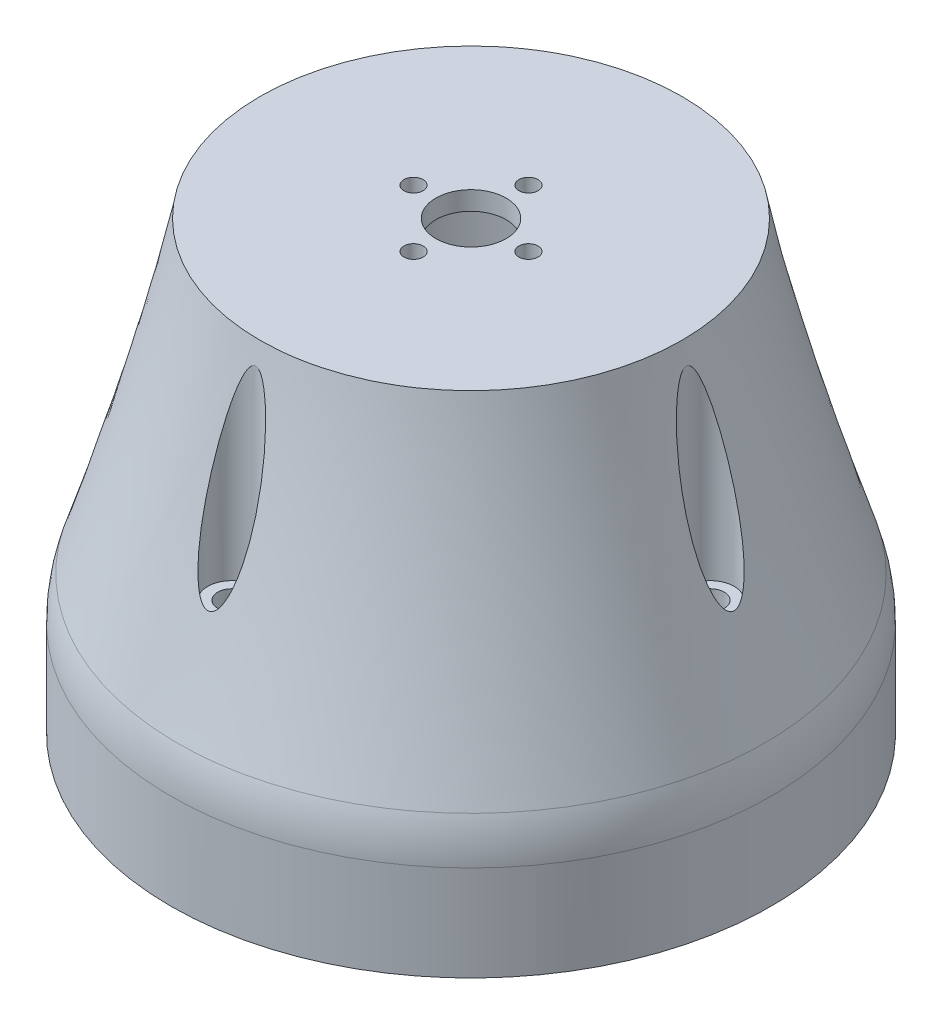
SolidWorks part; units mm, degrees
ref_plane "Front Plane" through (0, 0, 0) normal (0, 0, 1) x (1, 0, 0)
ref_plane "Top Plane" through (0, 0, 0) normal (0, 1, 0) x (1, 0, 0)
ref_plane "Right Plane" through (0, 0, 0) normal (1, 0, 0) x (0, 0, -1)
sketch "Sketch3" plane through (0, 0, 0) normal (0, 1, 0) x (1, 0, 0)
  circle A0 centre (0, 0) radius 64
  dimension "D1" = 128
extrude "Boss-Extrude1" add sketch "Sketch3" along normal blind 15
ref_plane "Plane1" through (0, 85, 0) normal (0, 1, 0) x (1, 0, 0)
sketch "Sketch4" plane through (0, 85, 0) normal (0, 1, 0) x (1, 0, 0)
  circle A0 centre (0, 0) radius 45
  dimension "D1" = 90
sketch "Sketch5" plane through (0, 15, 0) normal (0, 1, 0) x (1, 0, 0)
  circle A1 centre (0, 0) radius 64
  circle A2 centre (0, 0) radius 64
  dimension "D1" = 0
loft "Loft1" add profiles "Sketch5", "Sketch4" connector at (-2.5729, 15, 63.9483) connector at (15.8799, 85, 42.105)
fillet "Fillet1" radius 30 1 edges at (0, 15, 64) type face fillet first side face at (0, 15, 64) second side face at (0, 15, 64)
sketch "Sketch6" plane through (0, 85, 0) normal (0, 1, 0) x (1, 0, 0)
  circle A0 centre (0, 0) radius 51 construction
  circle A1 centre (0, 51) radius 3
  circle A2 centre (51, 0) radius 3
  circle A3 centre (0, -51) radius 3
  circle A4 centre (-51, 0) radius 3
  point P14 (0, 0)
  dimension "D1" = 102
  dimension "D2" = 6
  dimension "D3" = 4
extrude "Cut-Extrude1" cut sketch "Sketch6" against normal blind 85
sketch "Sketch8" plane through (0, 85, 0) normal (0, 1, 0) x (1, 0, 0)
  circle A0 centre (-51, 0) radius 5.11
  circle A1 centre (0, 51) radius 5.11
  circle A2 centre (51, 0) radius 5.11
  circle A3 centre (0, -51) radius 5.11
  point P12 (0, 0)
  dimension "D1" = 10.22
  dimension "D2" = 4
extrude "Cut-Extrude3" cut sketch "Sketch8" against normal blind 45
sketch "Sketch9" plane through (0, 0, 0) normal (0, -1, 0) x (1, 0, 0)
  arc A0 (-16.4684, 53.5238) -> (-53.5238, 16.4684) centre (0, 0) ccw
  arc A1 (-7.1314, 48.6777) -> (7.1314, 48.6777) centre (0, 51) ccw
  arc A5 (-7.1314, 48.6777) -> (-16.4684, 53.5238) centre (-14.2628, 46.3554) ccw
  arc A6 (16.4684, 53.5238) -> (7.1314, 48.6777) centre (14.2628, 46.3554) ccw
  arc A7 (48.6777, 7.1314) -> (53.5238, 16.4684) centre (46.3554, 14.2628) ccw
  arc A8 (48.6777, 7.1314) -> (48.6777, -7.1314) centre (51, 0) ccw
  arc A9 (53.5238, -16.4684) -> (48.6777, -7.1314) centre (46.3554, -14.2628) ccw
  arc A10 (7.1314, -48.6777) -> (16.4684, -53.5238) centre (14.2628, -46.3554) ccw
  arc A11 (7.1314, -48.6777) -> (-7.1314, -48.6777) centre (0, -51) ccw
  arc A12 (-16.4684, -53.5238) -> (-7.1314, -48.6777) centre (-14.2628, -46.3554) ccw
  arc A13 (-48.6777, -7.1314) -> (-53.5238, -16.4684) centre (-46.3554, -14.2628) ccw
  arc A14 (-48.6777, -7.1314) -> (-48.6777, 7.1314) centre (-51, 0) ccw
  arc A15 (-53.5238, 16.4684) -> (-48.6777, 7.1314) centre (-46.3554, 14.2628) ccw
  arc A16 (53.5238, 16.4684) -> (16.4684, 53.5238) centre (0, 0) ccw
  arc A17 (16.4684, -53.5238) -> (53.5238, -16.4684) centre (0, 0) ccw
  arc A18 (-53.5238, -16.4684) -> (-16.4684, -53.5238) centre (0, 0) ccw
  point P15 (0, 0)
  point P35 (0, 0)
  dimension "D1" = 112
  dimension "D2" = 15
  dimension "D3" = 4
  dimension "D4" = 15
  dimension "D5" = 15
extrude "Cut-Extrude4" cut sketch "Sketch9" against normal blind 12
sketch "Sketch17" plane through (0, 12, 0) normal (0, -1, 0) x (1, 0, 0)
  circle A0 centre (0, 0) radius 29
  dimension "D1" = 58
extrude "Cut-Extrude10" cut sketch "Sketch17" against normal blind 69
sketch "Sketch19" plane through (0, 0, 0) normal (0, -1, 0) x (1, 0, 0)
  arc A0 (16.4684, -53.5238) -> (53.5238, -16.4684) centre (0, 0) ccw construction
  circle A1 centre (0, 0) radius 64
  circle A2 centre (0, 0) radius 64
  arc A3 (53.5238, -16.4684) -> (48.6777, -7.1314) centre (46.3554, -14.2628) ccw construction
  arc A4 (48.6777, 7.1314) -> (48.6777, -7.1314) centre (51, 0) ccw construction
  arc A5 (48.6777, 7.1314) -> (53.5238, 16.4684) centre (46.3554, 14.2628) ccw construction
  arc A6 (53.5238, 16.4684) -> (16.4684, 53.5238) centre (0, 0) ccw construction
  arc A7 (-7.1314, 48.6777) -> (7.1314, 48.6777) centre (0, 51) ccw construction
  arc A8 (-7.1314, 48.6777) -> (-16.4684, 53.5238) centre (-14.2628, 46.3554) ccw construction
  arc A9 (16.4684, -53.5238) -> (53.5238, -16.4684) centre (0, 0) ccw
  arc A10 (53.5238, -16.4684) -> (48.6777, -7.1314) centre (46.3554, -14.2628) ccw
  arc A11 (48.6777, 7.1314) -> (48.6777, -7.1314) centre (51, 0) ccw
  arc A12 (48.6777, 7.1314) -> (53.5238, 16.4684) centre (46.3554, 14.2628) ccw
  arc A13 (53.5238, 16.4684) -> (16.4684, 53.5238) centre (0, 0) ccw
  arc A14 (-7.1314, 48.6777) -> (7.1314, 48.6777) centre (0, 51) ccw
  arc A15 (-7.1314, 48.6777) -> (-16.4684, 53.5238) centre (-14.2628, 46.3554) ccw
  arc A18 (16.4684, 53.5238) -> (7.1314, 48.6777) centre (14.2628, 46.3554) ccw
  arc A19 (-7.1314, 48.6777) -> (7.1314, 48.6777) centre (0, 51) ccw
  arc A20 (-7.1314, 48.6777) -> (-16.4684, 53.5238) centre (-14.2628, 46.3554) ccw
  arc A21 (-16.4684, 53.5238) -> (-53.5238, 16.4684) centre (0, 0) ccw
  arc A22 (-53.5238, 16.4684) -> (-48.6777, 7.1314) centre (-46.3554, 14.2628) ccw
  arc A23 (-48.6777, -7.1314) -> (-48.6777, 7.1314) centre (-51, 0) ccw
  arc A24 (-48.6777, -7.1314) -> (-53.5238, -16.4684) centre (-46.3554, -14.2628) ccw
  arc A25 (-53.5238, -16.4684) -> (-16.4684, -53.5238) centre (0, 0) ccw
  arc A26 (-16.4684, -53.5238) -> (-7.1314, -48.6777) centre (-14.2628, -46.3554) ccw
  arc A27 (7.1314, -48.6777) -> (-7.1314, -48.6777) centre (0, -51) ccw
  arc A28 (7.1314, -48.6777) -> (16.4684, -53.5238) centre (14.2628, -46.3554) ccw
  arc A29 (16.4684, -53.5238) -> (53.5238, -16.4684) centre (0, 0) ccw
  arc A30 (53.5238, -16.4684) -> (48.6777, -7.1314) centre (46.3554, -14.2628) ccw
  arc A31 (48.6777, 7.1314) -> (48.6777, -7.1314) centre (51, 0) ccw
  arc A32 (48.6777, 7.1314) -> (53.5238, 16.4684) centre (46.3554, 14.2628) ccw
  arc A33 (53.5238, 16.4684) -> (16.4684, 53.5238) centre (0, 0) ccw
  arc A34 (16.4684, 53.5238) -> (7.1314, 48.6777) centre (14.2628, 46.3554) ccw
  arc A35 (-7.1314, 48.6777) -> (7.1314, 48.6777) centre (0, 51) ccw
  arc A36 (-7.1314, 48.6777) -> (-16.4684, 53.5238) centre (-14.2628, 46.3554) ccw
  arc A37 (-16.4684, 53.5238) -> (-53.5238, 16.4684) centre (0, 0) ccw
  arc A38 (-53.5238, 16.4684) -> (-48.6777, 7.1314) centre (-46.3554, 14.2628) ccw
  arc A39 (-48.6777, -7.1314) -> (-48.6777, 7.1314) centre (-51, 0) ccw
  arc A40 (-48.6777, -7.1314) -> (-53.5238, -16.4684) centre (-46.3554, -14.2628) ccw
  arc A41 (-53.5238, -16.4684) -> (-16.4684, -53.5238) centre (0, 0) ccw
  arc A42 (-16.4684, -53.5238) -> (-7.1314, -48.6777) centre (-14.2628, -46.3554) ccw
  arc A43 (7.1314, -48.6777) -> (-7.1314, -48.6777) centre (0, -51) ccw
  arc A44 (7.1314, -48.6777) -> (16.4684, -53.5238) centre (14.2628, -46.3554) ccw
  arc A45 (16.4684, -53.5238) -> (53.5238, -16.4684) centre (0, 0) ccw
  arc A46 (53.5238, -16.4684) -> (48.6777, -7.1314) centre (46.3554, -14.2628) ccw
  arc A47 (48.6777, 7.1314) -> (48.6777, -7.1314) centre (51, 0) ccw
  arc A48 (48.6777, 7.1314) -> (53.5238, 16.4684) centre (46.3554, 14.2628) ccw
  arc A49 (53.5238, 16.4684) -> (16.4684, 53.5238) centre (0, 0) ccw
  circle M19 centre (0, -51) radius 3
  circle M20 centre (51, 0) radius 3
  circle M21 centre (0, 51) radius 3
  circle M22 centre (-51, 0) radius 3
  circle M23 centre (0, 0) radius 64
  arc M24 (-7.1314, 48.6777) -> (7.1314, 48.6777) centre (0, 51) ccw
  arc M25 (7.1314, 48.6777) -> (16.4684, 53.5238) centre (14.2628, 46.3554) cw
  arc M26 (16.4684, 53.5238) -> (53.5238, 16.4684) centre (0, 0) cw
  arc M27 (53.5238, 16.4684) -> (48.6777, 7.1314) centre (46.3554, 14.2628) cw
  arc M28 (48.6777, 7.1314) -> (48.6777, -7.1314) centre (51, 0) ccw
  arc M29 (48.6777, -7.1314) -> (53.5238, -16.4684) centre (46.3554, -14.2628) cw
  arc M30 (53.5238, -16.4684) -> (16.4684, -53.5238) centre (0, 0) cw
  arc M31 (16.4684, -53.5238) -> (7.1314, -48.6777) centre (14.2628, -46.3554) cw
  arc M32 (7.1314, -48.6777) -> (-7.1314, -48.6777) centre (0, -51) ccw
  arc M33 (-7.1314, -48.6777) -> (-16.4684, -53.5238) centre (-14.2628, -46.3554) cw
  arc M34 (-16.4684, -53.5238) -> (-53.5238, -16.4684) centre (0, 0) cw
  arc M35 (-53.5238, -16.4684) -> (-48.6777, -7.1314) centre (-46.3554, -14.2628) cw
  arc M36 (-48.6777, -7.1314) -> (-48.6777, 7.1314) centre (-51, 0) ccw
  arc M37 (-48.6777, 7.1314) -> (-53.5238, 16.4684) centre (-46.3554, 14.2628) cw
  arc M38 (-53.5238, 16.4684) -> (-16.4684, 53.5238) centre (0, 0) cw
  arc M39 (-16.4684, 53.5238) -> (-7.1314, 48.6777) centre (-14.2628, 46.3554) cw
  dimension "D1" = 0
  dimension "D2" = 0
extrude "Boss-Extrude3" add sketch "Sketch19" along normal blind 10 contours M23 M20 M22 M39 M24 M25 M26 M27 M28 M29 M30 M31 M32 M33 M34 M35 M36 M37 M38 M21 M19 region at (-62.1898, 0, 0)
sketch "Sketch20" plane through (0, 85, 0) normal (0, 1, 0) x (1, 0, 0)
  circle A0 centre (0, 0) radius 12.25 construction
  circle A1 centre (0, 0) radius 7.5
  circle A2 centre (0, 12.25) radius 2.05
  circle A3 centre (12.25, 0) radius 2.05
  circle A4 centre (0, -12.25) radius 2.05
  circle A5 centre (-12.25, 0) radius 2.05
  point P15 (0, 0)
  dimension "D1" = 24.5
  dimension "D2" = 15
  dimension "D3" = 4.1
  dimension "D4" = 4
extrude "Cut-Extrude12" cut sketch "Sketch20" against normal blind 10
sketch "Sketch21" plane through (0, 0, 0) normal (0, 0, 1) x (1, 0, 0)
  line L0 (0, 0) -> (0, 38.5094) construction
  line L2 (-29, 73.5) -> (-35, 73.5)
  line L3 (-29, 73.5) -> (-29, 68.5)
  line L4 (-29, 68.5) -> (-35, 68.5)
  line L5 (-37, 71.5) -> (-37, 70.5)
  line L6 (-29, 73.5) -> (-37, 68.5) construction
  line L7 (-29, 68.5) -> (-37, 73.5) construction
  arc A1 (-35, 68.5) -> (-37, 70.5) centre (-35, 70.5) cw
  arc A2 (-37, 71.5) -> (-35, 73.5) centre (-35, 71.5) cw
  point P7 (-33, 71)
  point P10 (-31.5189, 71)
  dimension "D3" = 5
  dimension "D5" = 2
  dimension "D1" = 71
  dimension "D2" = 33
  dimension "D4" = 8
revolve "Cut-Revolve1" cut sketch "Sketch21" angle 20 mid plane about L0
sketch "Sketch22" plane through (0, 68.5, 0) normal (0, 1, 0) x (1, 0, 0)
  line L2 (-34.4683, -6.0777) -> (-28.5594, -5.0358)
  line L3 (-28.5594, 5.0358) -> (-34.4683, 6.0777)
  line L4 (-34.4683, -6.0777) -> (-28.5594, -5.0358)
  line L5 (-28.5594, 5.0358) -> (-34.4683, 6.0777)
  arc A2 (-34.4683, 6.0777) -> (-34.4683, -6.0777) centre (0, 0) ccw
  arc A3 (-28.5594, 5.0358) -> (-28.5594, -5.0358) centre (0, 0) ccw
  arc A4 (-34.4683, 6.0777) -> (-34.4683, -6.0777) centre (0, 0) ccw
  arc A5 (-28.5594, 5.0358) -> (-28.5594, -5.0358) centre (0, 0) ccw
  dimension "D1" = 0
extrude "Cut-Extrude13" cut sketch "Sketch22" against normal up to surface (56.5 mm away) up to face at (0, 12, -29)
